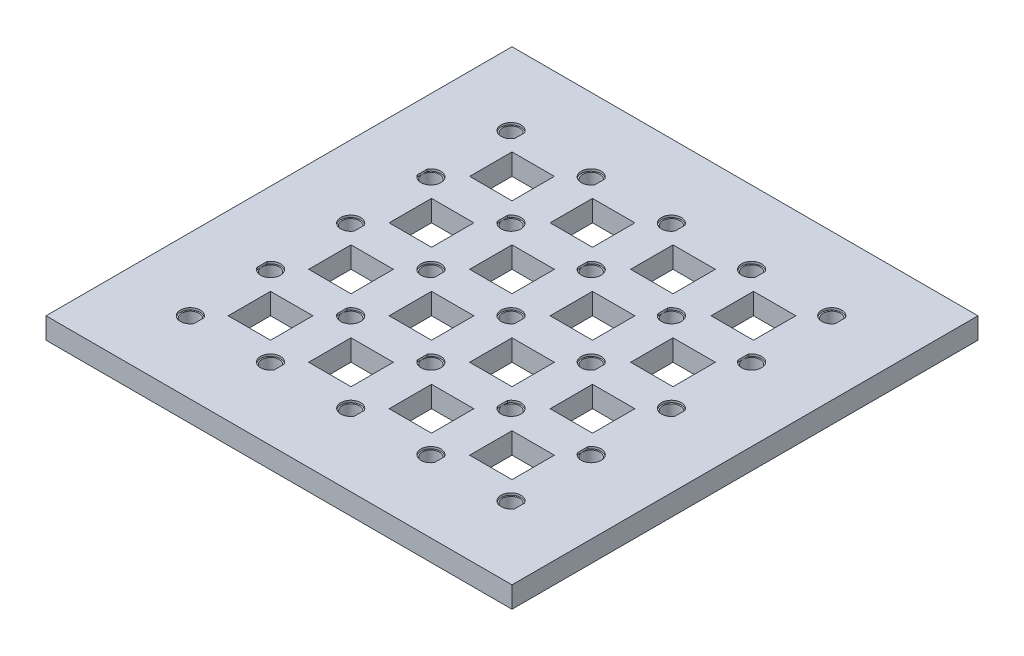
SolidWorks part; units mm, degrees
ref_plane "Front Plane" through (0, 0, 0) normal (0, 0, 1) x (1, 0, 0)
ref_plane "Top Plane" through (0, 0, 0) normal (0, 1, 0) x (1, 0, 0)
ref_plane "Right Plane" through (0, 0, 0) normal (1, 0, 0) x (0, 0, -1)
sketch "Sketch1" plane through (0, 0, 0) normal (0, 1, 0) x (1, 0, 0)
  line L1 (-110, -110) -> (110, -110)
  line L2 (-110, -110) -> (-110, 110)
  line L3 (-110, 110) -> (110, 110)
  line L4 (110, -110) -> (110, 110)
  line L5 (-110, -110) -> (110, 110) construction
  line L6 (-110, 110) -> (110, -110) construction
  point P0 (0, 0)
  dimension "D1" = 220
  dimension "D2" = 220
extrude "Boss-Extrude1" add sketch "Sketch1" along normal blind 10
sketch "Sketch2" plane through (0, 10, 0) normal (0, 1, 0) x (1, 0, 0)
  line L1 (-110, 110) -> (-110, -110) construction
  line L3 (-110, -110) -> (110, -110) construction
  circle A0 centre (-75.925, -75.925) radius 4.075
  circle A1 centre (-38.075, -75.925) radius 4.075
  circle A2 centre (-0.225, -75.925) radius 4.075
  circle A3 centre (37.625, -75.925) radius 4.075
  circle A4 centre (75.475, -75.925) radius 4.075
  circle A5 centre (-75.925, -38.075) radius 4.075
  circle A6 centre (-38.075, -38.075) radius 4.075
  circle A7 centre (-0.225, -38.075) radius 4.075
  circle A8 centre (37.625, -38.075) radius 4.075
  circle A9 centre (75.475, -38.075) radius 4.075
  circle A10 centre (-75.925, -0.225) radius 4.075
  circle A11 centre (-38.075, -0.225) radius 4.075
  circle A12 centre (-0.225, -0.225) radius 4.075
  circle A13 centre (37.625, -0.225) radius 4.075
  circle A14 centre (75.475, -0.225) radius 4.075
  circle A15 centre (-75.925, 37.625) radius 4.075
  circle A16 centre (-38.075, 37.625) radius 4.075
  circle A17 centre (-0.225, 37.625) radius 4.075
  circle A18 centre (37.625, 37.625) radius 4.075
  circle A19 centre (75.475, 37.625) radius 4.075
  circle A20 centre (-75.925, 75.475) radius 4.075
  circle A21 centre (-38.075, 75.475) radius 4.075
  circle A22 centre (-0.225, 75.475) radius 4.075
  circle A23 centre (37.625, 75.475) radius 4.075
  circle A24 centre (75.475, 75.475) radius 4.075
  dimension "D1" = 8.15
  dimension "D5" = 29.7
  dimension "D7" = 29.7
  dimension "D2" = 30
  dimension "D3" = 30
  dimension "D4" = 5
  dimension "D6" = 5
extrude "Cut-Extrude1" cut sketch "Sketch2" against normal blind 10
sketch "Sketch3" plane through (0, 10, 0) normal (0, 1, 0) x (1, 0, 0)
  line L0 (-71.85, -78.2669) -> (-71.85, -73.5831)
  line L5 (-80, -35.7331) -> (-80, -40.4169)
  line L10 (-71.85, -2.5669) -> (-71.85, 2.1169)
  line L11 (-80, 39.9669) -> (-80, 35.2831)
  line L12 (-71.85, 73.1331) -> (-71.85, 77.8169)
  line L13 (-34, 73.1331) -> (-34, 77.8169)
  line L14 (-42.15, 39.9669) -> (-42.15, 35.2831)
  line L15 (-34, -2.5669) -> (-34, 2.1169)
  line L16 (-34, -78.2669) -> (-34, -73.5831)
  line L17 (-42.15, -35.7331) -> (-42.15, -40.4169)
  line L18 (3.85, 73.1331) -> (3.85, 77.8169)
  line L19 (-4.3, 39.9669) -> (-4.3, 35.2831)
  line L20 (3.85, -2.5669) -> (3.85, 2.1169)
  line L21 (3.85, -78.2669) -> (3.85, -73.5831)
  line L22 (-4.3, -35.7331) -> (-4.3, -40.4169)
  line L23 (41.7, 73.1331) -> (41.7, 77.8169)
  line L24 (33.55, 39.9669) -> (33.55, 35.2831)
  line L25 (41.7, -2.5669) -> (41.7, 2.1169)
  line L26 (41.7, -78.2669) -> (41.7, -73.5831)
  line L27 (33.55, -35.7331) -> (33.55, -40.4169)
  line L28 (79.55, 73.1331) -> (79.55, 77.8169)
  line L29 (71.4, 39.9669) -> (71.4, 35.2831)
  line L30 (79.55, -2.5669) -> (79.55, 2.1169)
  line L31 (79.55, -78.2669) -> (79.55, -73.5831)
  line L32 (71.4, -35.7331) -> (71.4, -40.4169)
  arc A0 (-71.85, -73.5831) -> (-71.85, -78.2669) centre (-75.925, -75.925) ccw
  circle A1 centre (-75.925, -75.925) radius 4.075 construction
  arc A6 (-80, -40.4169) -> (-80, -35.7331) centre (-75.925, -38.075) ccw
  circle A7 centre (-75.925, -38.075) radius 4.075 construction
  arc A12 (-71.85, 2.1169) -> (-71.85, -2.5669) centre (-75.925, -0.225) ccw
  arc A13 (-80, 35.2831) -> (-80, 39.9669) centre (-75.925, 37.625) ccw
  circle A14 centre (-75.925, -0.225) radius 4.075 construction
  circle A15 centre (-75.925, 37.625) radius 4.075 construction
  arc A16 (-71.85, 77.8169) -> (-71.85, 73.1331) centre (-75.925, 75.475) ccw
  circle A17 centre (-75.925, 75.475) radius 4.075 construction
  arc A18 (-34, 77.8169) -> (-34, 73.1331) centre (-38.075, 75.475) ccw
  arc A19 (-42.15, 35.2831) -> (-42.15, 39.9669) centre (-38.075, 37.625) ccw
  arc A20 (-34, 2.1169) -> (-34, -2.5669) centre (-38.075, -0.225) ccw
  arc A21 (-34, -73.5831) -> (-34, -78.2669) centre (-38.075, -75.925) ccw
  arc A22 (-42.15, -40.4169) -> (-42.15, -35.7331) centre (-38.075, -38.075) ccw
  arc A23 (3.85, 77.8169) -> (3.85, 73.1331) centre (-0.225, 75.475) ccw
  arc A24 (-4.3, 35.2831) -> (-4.3, 39.9669) centre (-0.225, 37.625) ccw
  arc A25 (3.85, 2.1169) -> (3.85, -2.5669) centre (-0.225, -0.225) ccw
  arc A26 (3.85, -73.5831) -> (3.85, -78.2669) centre (-0.225, -75.925) ccw
  arc A27 (-4.3, -40.4169) -> (-4.3, -35.7331) centre (-0.225, -38.075) ccw
  arc A28 (41.7, 77.8169) -> (41.7, 73.1331) centre (37.625, 75.475) ccw
  arc A29 (33.55, 35.2831) -> (33.55, 39.9669) centre (37.625, 37.625) ccw
  arc A30 (41.7, 2.1169) -> (41.7, -2.5669) centre (37.625, -0.225) ccw
  arc A31 (41.7, -73.5831) -> (41.7, -78.2669) centre (37.625, -75.925) ccw
  arc A32 (33.55, -40.4169) -> (33.55, -35.7331) centre (37.625, -38.075) ccw
  arc A33 (79.55, 77.8169) -> (79.55, 73.1331) centre (75.475, 75.475) ccw
  arc A34 (71.4, 35.2831) -> (71.4, 39.9669) centre (75.475, 37.625) ccw
  arc A35 (79.55, 2.1169) -> (79.55, -2.5669) centre (75.475, -0.225) ccw
  arc A36 (79.55, -73.5831) -> (79.55, -78.2669) centre (75.475, -75.925) ccw
  arc A37 (71.4, -40.4169) -> (71.4, -35.7331) centre (75.475, -38.075) ccw
  point P0 (-75.925, -75.925)
  point P7 (-75.925, 75.475)
  point P11 (-75.925, 75.475)
  point P15 (0, 0)
  point P21 (-75.925, -38.075)
  point P26 (-75.925, -38.075)
  point P31 (-75.925, 37.625)
  point P51 (-75.925, -0.225)
  point P56 (-75.925, 37.625)
  point P60 (-75.925, 37.625)
  point P61 (-75.925, -0.225)
  point P102 (-38.075, -75.925)
  dimension "D1" = 4.7
  dimension "D3" = 4.7
  dimension "D5" = 4.7
  dimension "D6" = 4.7
  dimension "D2" = 4.7
extrude "Cut-Extrude2" cut sketch "Sketch3" against normal blind 1
sketch "Sketch4" plane through (0, 10, 0) normal (0, 1, 0) x (1, 0, 0)
  line L0 (-110, 110) -> (-110, -110) construction
  line L1 (-67, 47) -> (-47, 47)
  line L2 (-67, 47) -> (-67, 67)
  line L3 (-67, 67) -> (-47, 67)
  line L4 (-47, 47) -> (-47, 67)
  line L5 (-67, 47) -> (-47, 67) construction
  line L6 (-67, 67) -> (-47, 47) construction
  line L7 (110, 110) -> (-110, 110) construction
  line L8 (-29, 67) -> (-9, 67)
  line L9 (-29, 47) -> (-29, 67)
  line L10 (-29, 47) -> (-9, 47)
  line L11 (-9, 47) -> (-9, 67)
  line L12 (9, 67) -> (29, 67)
  line L13 (9, 47) -> (9, 67)
  line L14 (9, 47) -> (29, 47)
  line L15 (29, 47) -> (29, 67)
  line L16 (47, 67) -> (67, 67)
  line L17 (47, 47) -> (47, 67)
  line L18 (47, 47) -> (67, 47)
  line L19 (67, 47) -> (67, 67)
  line L20 (-29, 29) -> (-9, 29)
  line L21 (-29, 9) -> (-29, 29)
  line L22 (-29, 9) -> (-9, 9)
  line L23 (-9, 9) -> (-9, 29)
  line L24 (9, 29) -> (29, 29)
  line L25 (9, 9) -> (9, 29)
  line L26 (9, 9) -> (29, 9)
  line L27 (29, 9) -> (29, 29)
  line L28 (47, 29) -> (67, 29)
  line L29 (47, 9) -> (47, 29)
  line L30 (47, 9) -> (67, 9)
  line L31 (67, 9) -> (67, 29)
  line L32 (-67, 29) -> (-47, 29)
  line L33 (-67, 9) -> (-67, 29)
  line L34 (-67, 9) -> (-47, 9)
  line L35 (-47, 9) -> (-47, 29)
  line L36 (-29, -9) -> (-9, -9)
  line L37 (-29, -29) -> (-29, -9)
  line L38 (-29, -29) -> (-9, -29)
  line L39 (-9, -29) -> (-9, -9)
  line L40 (9, -9) -> (29, -9)
  line L41 (9, -29) -> (9, -9)
  line L42 (9, -29) -> (29, -29)
  line L43 (29, -29) -> (29, -9)
  line L44 (47, -9) -> (67, -9)
  line L45 (47, -29) -> (47, -9)
  line L46 (47, -29) -> (67, -29)
  line L47 (67, -29) -> (67, -9)
  line L48 (-67, -9) -> (-47, -9)
  line L49 (-67, -29) -> (-67, -9)
  line L50 (-67, -29) -> (-47, -29)
  line L51 (-47, -29) -> (-47, -9)
  line L52 (-29, -47) -> (-9, -47)
  line L53 (-29, -67) -> (-29, -47)
  line L54 (-29, -67) -> (-9, -67)
  line L55 (-9, -67) -> (-9, -47)
  line L56 (9, -47) -> (29, -47)
  line L57 (9, -67) -> (9, -47)
  line L58 (9, -67) -> (29, -67)
  line L59 (29, -67) -> (29, -47)
  line L60 (47, -47) -> (67, -47)
  line L61 (47, -67) -> (47, -47)
  line L62 (47, -67) -> (67, -67)
  line L63 (67, -67) -> (67, -47)
  line L64 (-67, -47) -> (-47, -47)
  line L65 (-67, -67) -> (-67, -47)
  line L66 (-67, -67) -> (-47, -67)
  line L67 (-47, -67) -> (-47, -47)
  point P0 (-57, 57)
  dimension "D1" = 53
  dimension "D2" = 20
  dimension "D3" = 20
  dimension "D4" = 53
  dimension "D6" = 18
  dimension "D8" = 18
  dimension "D5" = 4
  dimension "D7" = 4
extrude "Cut-Extrude3" cut sketch "Sketch4" against normal through all
